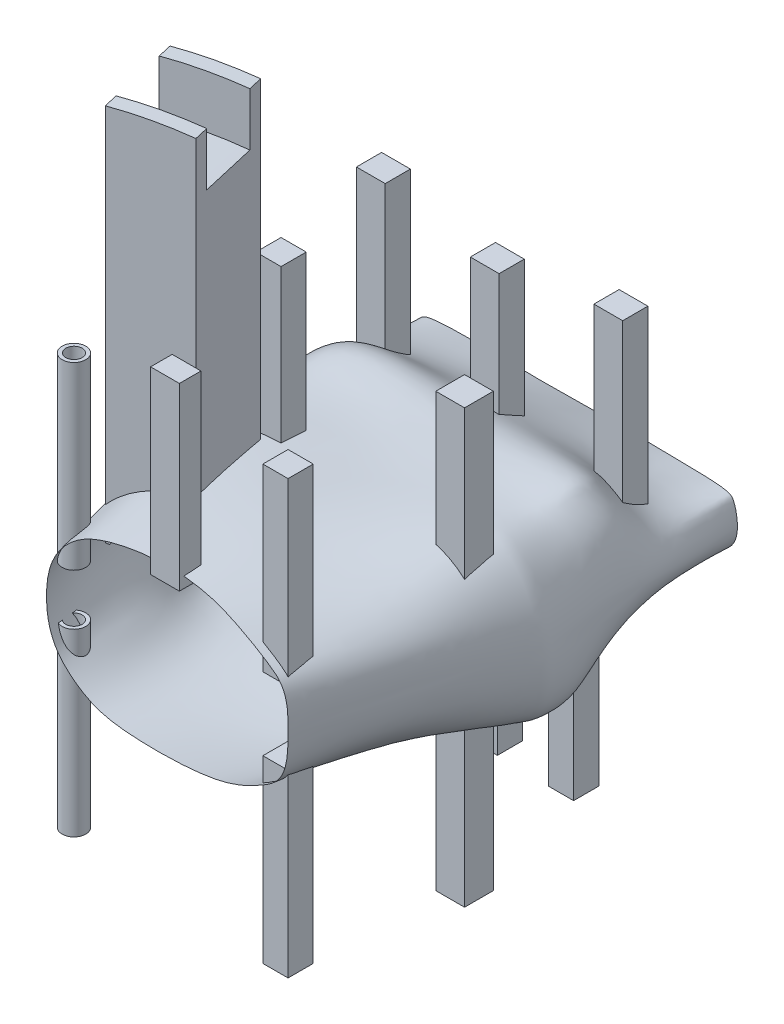
SolidWorks part; units mm, degrees
ref_plane "Front Plane" through (0, 0, 0) normal (0, 0, 1) x (1, 0, 0)
ref_plane "Top Plane" through (0, 0, 0) normal (0, 1, 0) x (1, 0, 0)
ref_plane "Right Plane" through (0, 0, 0) normal (1, 0, 0) x (0, 0, -1)
sketch "Sketch1" plane through (0, 8, 0) normal (0, 1, 0) x (1, 0, 0)
  line L1 (-4, -2.5) -> (4, -2.5)
  line L2 (-4, -2.5) -> (-4, -9.5)
  line L3 (-4, -9.5) -> (4, -9.5)
  line L4 (4, -2.5) -> (4, -9.5)
  line L5 (62, -2.5) -> (70, -2.5)
  line L6 (62, -2.5) -> (62, -9.5)
  line L7 (62, -9.5) -> (70, -9.5)
  line L8 (70, -2.5) -> (70, -9.5)
extrude "Boss-Extrude1" add sketch "Sketch1" along normal blind 50 from offset 0.1
sketch "Sketch2" plane through (0, 4, 0) normal (0, 1, 0) x (1, 0, 0)
  line L10 (37.5, -11.35) -> (37.5, -4.35)
  line L11 (37.5, -4.35) -> (29.5, -4.35)
  line L12 (29.5, -4.35) -> (29.5, -11.35)
  line L13 (29.5, -11.35) -> (33.75, -11.35)
  line L14 (33.75, -11.35) -> (37.5, -11.35)
  line L15 (37.5, -11.35) -> (37.5, -4.35)
  line L16 (37.5, -4.35) -> (29.5, -4.35)
  line L17 (29.5, -4.35) -> (29.5, -11.35)
  line L18 (29.5, -11.35) -> (33.75, -11.35)
  line L19 (33.75, -11.35) -> (37.5, -11.35)
  dimension "D1" = 0.2
extrude "Boss-Extrude2" add sketch "Sketch2" along normal blind 50 from offset 0.1 separate body
sketch "Sketch3" plane through (0, 9, 0) normal (0, 1, 0) x (1, 0, 0)
  line L1 (-9.75, -44.95) -> (-2.75, -44.95)
  line L2 (-9.75, -44.95) -> (-9.75, -51.95)
  line L3 (-9.75, -51.95) -> (-2.75, -51.95)
  line L4 (-2.75, -44.95) -> (-2.75, -51.95)
extrude "Boss-Extrude3" add sketch "Sketch3" along normal blind 50 from offset 0.1 separate body
sketch "Sketch4" plane through (0, 16, 0) normal (0, 1, 0) x (1, 0, 0)
  line L4 (17.5, -51.95) -> (17.5, -44.95)
  line L5 (17.5, -44.95) -> (10.5, -44.95)
  line L6 (10.5, -44.95) -> (10.5, -51.95)
  line L7 (10.5, -51.95) -> (17.5, -51.95)
  line L8 (17.5, -51.95) -> (17.5, -44.95)
  line L9 (17.5, -44.95) -> (10.5, -44.95)
  line L10 (10.5, -44.95) -> (10.5, -51.95)
  line L11 (10.5, -51.95) -> (17.5, -51.95)
  dimension "D1" = 0
extrude "Boss-Extrude4" add sketch "Sketch4" along normal blind 50 from offset 0.1 separate body
sketch "Sketch5" plane through (0, 8, 0) normal (0, 1, 0) x (1, 0, 0)
  line L4 (61, -52.45) -> (69, -52.45)
  line L5 (69, -52.45) -> (69, -44.45)
  line L6 (69, -44.45) -> (61, -44.45)
  line L7 (61, -44.45) -> (61, -52.45)
  line L8 (61, -52.45) -> (69, -52.45)
  line L9 (69, -52.45) -> (69, -44.45)
  line L10 (69, -44.45) -> (61, -44.45)
  line L11 (61, -44.45) -> (61, -52.45)
  dimension "D1" = 0
extrude "Boss-Extrude5" add sketch "Sketch5" along normal blind 50 from offset 0.1 separate body
sketch "Sketch6" plane through (0, 9, 0) normal (0, 1, 0) x (1, 0, 0)
  line L4 (55.5, -95) -> (62.5, -95)
  line L5 (62.5, -95) -> (62.5, -88)
  line L6 (62.5, -88) -> (55.5, -88)
  line L7 (55.5, -88) -> (55.5, -95)
  line L8 (55.5, -95) -> (62.5, -95)
  line L9 (62.5, -95) -> (62.5, -88)
  line L10 (62.5, -88) -> (55.5, -88)
  line L11 (55.5, -88) -> (55.5, -95)
  dimension "D1" = 0
extrude "Boss-Extrude6" add sketch "Sketch6" along normal blind 50 from offset 0.1 separate body
sketch "Sketch7" plane through (0, 20, 0) normal (0, 1, 0) x (1, 0, 0)
  line L8 (35.5, -92.2) -> (27.5, -92.2)
  line L9 (27.5, -92.2) -> (27.5, -98.2)
  line L10 (27.5, -98.2) -> (35.5, -98.2)
  line L11 (35.5, -98.2) -> (35.5, -92.2)
  line L12 (35.5, -92.2) -> (27.5, -92.2)
  line L13 (27.5, -92.2) -> (27.5, -98.2)
  line L14 (27.5, -98.2) -> (35.5, -98.2)
  line L15 (35.5, -98.2) -> (35.5, -92.2)
  dimension "D1" = 0.2
extrude "Boss-Extrude7" add sketch "Sketch7" along normal blind 50 from offset 0.1 separate body
sketch "Sketch8" plane through (0, 6, 0) normal (0, 1, 0) x (1, 0, 0)
  circle A0 centre (-0.5, -91.5) radius 2.275
  circle A1 centre (-0.5, -91.5) radius 3.275
  arc A2 (-1.6902, -94.5511) -> (-1.0727, -88.2755) centre (-0.5, -91.5) ccw construction
  circle A3 centre (-0.5, -91.5) radius 2.275 construction
extrude "Boss-Extrude8" add sketch "Sketch8" along normal blind 50 from offset 0.1 separate body
sketch "Sketch9" plane through (0, -12, 0) normal (0, -1, 0) x (1, 0, 0)
  line L1 (7.5, 11.65) -> (14.5, 11.65)
  line L2 (7.5, 11.65) -> (7.5, 4.65)
  line L3 (7.5, 4.65) -> (14.5, 4.65)
  line L4 (14.5, 11.65) -> (14.5, 4.65)
  line L5 (30, 11.35) -> (37, 11.35)
  line L6 (30, 11.35) -> (30, 4.35)
  line L7 (30, 4.35) -> (37, 4.35)
  line L8 (37, 11.35) -> (37, 4.35)
  line L9 (58.5, 11.65) -> (51.5, 11.65)
  line L10 (58.5, 11.65) -> (58.5, 4.65)
  line L11 (58.5, 4.65) -> (51.5, 4.65)
  line L12 (51.5, 11.65) -> (51.5, 4.65)
  line L13 (61, 52.45) -> (69, 52.45)
  line L14 (61, 52.45) -> (61, 44.45)
  line L15 (61, 44.45) -> (69, 44.45)
  line L16 (69, 52.45) -> (69, 44.45)
extrude "Boss-Extrude9" add sketch "Sketch9" along normal blind 50 from offset 0.1 separate body
sketch "Sketch10" plane through (0, -11, 0) normal (0, -1, 0) x (1, 0, 0)
  line L1 (55.5, 95) -> (62.5, 95)
  line L2 (55.5, 95) -> (55.5, 88)
  line L3 (55.5, 88) -> (62.5, 88)
  line L4 (62.5, 95) -> (62.5, 88)
  line L5 (17.5, 51.95) -> (10.5, 51.95)
  line L6 (17.5, 51.95) -> (17.5, 44.95)
  line L7 (17.5, 44.95) -> (10.5, 44.95)
  line L8 (10.5, 51.95) -> (10.5, 44.95)
extrude "Boss-Extrude10" add sketch "Sketch10" along normal blind 50 from offset 0.1 separate body
sketch "Sketch11" plane through (0, -8, 0) normal (0, -1, 0) x (1, 0, 0)
  circle A0 centre (-0.5, 91.5) radius 2.275 construction
  circle A1 centre (-0.5, 91.5) radius 3.275
  circle A2 centre (-0.5, 91.5) radius 3.275
  circle A3 centre (-0.5, 91.5) radius 2.275
  dimension "D1" = 0
extrude "Boss-Extrude11" add sketch "Sketch11" along normal blind 50 from offset 0.1 separate body
ref_plane "Plane1" through (12.8977, 0, 55.8661) normal (0.225, 0, 0.9744) x (0.9744, 0, -0.225)
ref_plane "Plane2" through (15.1472, 0, 65.6098) normal (0.225, 0, 0.9744) x (0.9744, 0, -0.225)
sketch "Sketch12" plane through (12.8977, 0, 55.8661) normal (0.225, 0, 0.9744) x (0.9744, 0, -0.225)
  circle A0 centre (-9.3704, 0) radius 10.7
  dimension "D1" = 21.4
extrude "Extrude-Thin1" add sketch "Sketch12" along normal mid plane 4 separate body thin thin type one direction wall 100
sketch "Sketch13" plane through (13.3476, 0, 57.8148) normal (0.225, 0, 0.9744) x (0.9744, 0, -0.225)
  line L0 (0.0896, 5) -> (1.1296, 5)
  line L1 (1.1296, 5) -> (1.1296, 110.2009)
  line L2 (-19.8704, 110.2009) -> (-19.8704, 5)
  line L3 (-20.0704, 6) -> (-20.0704, 0) construction
  line L4 (1.3296, 6) -> (1.3296, 0) construction
  line L5 (-19.8704, 5) -> (-18.8303, 5)
  line L6 (-15.9888, 6) -> (-22.9251, 6) construction
  circle A0 centre (-9.3704, 0) radius 10.7 construction
  circle A1 centre (-9.3704, 0) radius 110.7 construction
  arc A2 (-19.8704, 110.2009) -> (1.1296, 110.2009) centre (-9.3704, 0) ccw
  arc A3 (0.0896, 5) -> (-18.8303, 5) centre (-9.3704, 0) ccw
  dimension "D1" = 0.2
  dimension "D2" = 0.2
  dimension "D3" = 1
extrude "Cut-Extrude1" cut sketch "Sketch13" against normal through all both and the other way through all
mirror "Mirror1" about plane through (15.1472, 0, 65.6098) normal (0.225, 0, 0.9744) of bodies 118
sketch "Sketch14" plane through (17.8466, 0, 77.3022) normal (0.225, 0, 0.9744) x (0.9744, 0, -0.225)
  circle A0 centre (-9.3704, 0) radius 16
  dimension "D1" = 32
extrude "Extrude-Thin2" add sketch "Sketch14" against normal up to surface (24 mm away) thin up to face at (3.3176, 41.1002, 56.0252) thin type one direction wall 80
extrude "Cut-Extrude2" cut sketch "Sketch13<3>" against normal through all both and the other way through all
sketch "Sketch13<3>" plane through (13.3476, 0, 57.8148) normal (0.225, 0, 0.9744) x (0.9744, 0, -0.225) same geometry as "Sketch13"
fillet "Fillet1" radius 0.5 2 edges at (16.2479, 12.0727, 65.3557) (-4.2139, 12.0727, 70.0796)
ref_plane "Plane3" through (0, 0, 0) normal (0, 1, 0) x (1, 0, 0)
sketch "Sketch15" plane through (0, 0, 0) normal (0, 1, 0) x (1, 0, 0)
  line L0 (-12.1525, 15) -> (-15.2953, -40.3087)
  line L1 (-15.0551, -43.1255) -> (-2.294, -98.4)
  line L2 (64.1595, -98.4) -> (79.2818, -41.9628)
  line L3 (79.614, -38.9613) -> (77.3822, 15)
  line L4 (76.3839, -33.4595) -> (75, 0) construction
  line L5 (76.7992, -43.5006) -> (63.0268, -94.9) construction
  line L6 (-12.3568, -41.4768) -> (-8.5998, -57.7502) construction
  line L7 (-10, 0) -> (-12.2621, -39.8092) construction
  line L9 (64.1595, -98.4) -> (65.0973, -94.9)
  line L10 (-2.294, -98.4) -> (-3.102, -94.9)
  line L12 (75, 0) -> (47, 0) construction
  arc A0 (79.2818, -41.9628) -> (79.614, -38.9613) centre (69.6226, -39.3746) ccw
  arc A1 (-15.2953, -40.3087) -> (-15.0551, -43.1255) centre (-5.3114, -40.876) ccw
  point P14 (0, 0)
  point P24 (0, 0)
  point P25 (63.9468, -99.1937)
  point P26 (0, 0)
  point P28 (0, 0)
  point P30 (0, 0)
  point P32 (0, 0)
  point P33 (-11.5291, 25.9717)
  point P34 (0, 0)
  point P35 (77.212, 19.1146)
  point P36 (77.0804, 22.2963)
  dimension "D5" = 10
  dimension "D1" = 3
  dimension "D2" = 2
  dimension "D3" = 3
  dimension "D4" = 3
  dimension "D6" = 15
ref_plane "Plane4" through (0, 0, -15) normal (0, 0, -1) x (-1, 0, 0)
ref_plane "Plane5" through (0, 0, 41.97) normal (0, 0, 1) x (1, 0, 0)
ref_plane "Plane6" through (0, 0, 29.03) normal (0, 0, -1) x (-1, 0, 0)
ref_plane "Plane7" through (0, 0, 67.45) normal (0, 0, 1) x (1, 0, 0)
ref_plane "Plane8" through (0, 0, 97) normal (0, 0, 1) x (1, 0, 0)
sketch "Sketch16" plane through (0, 0, -15) normal (0, 0, -1) x (-1, 0, 0)
  line L0 (-64.1595, 0) -> (-79.2818, 0) construction
  line L1 (-79.614, 0) -> (-77.3822, 0) construction
  line L2 (15.0551, 0) -> (2.294, 0) construction
  spline S0 degree 3 poles (-71.1852, -9.0827) (-78.6693, -4.8815) (-76.8048, 5.1779) (-74.9375, 7.6273) (-44.2299, 7.9457) (-51.3054, 8.2091) (-16.6288, 7.6603) (-20.5035, 8.0278) (8.9045, 8.0076) (11.3889, 5.5481) (12.2889, 1.7755) (11.9298, -3.3745) (11.1196, -8.9657) (-11.6903, -7.8226) (-16.6557, -9.5364) (-48.9186, -8.3026) (-56.5707, -7.9846) (-71.1852, -9.0827) (-78.6693, -4.8815) (-76.8048, 5.1779) knots -0.231953 -0.094003 -0.053059 0 0.019528 0.023803 0.04275 0.118919 0.206181 0.302051 0.336436 0.343183 0.366589 0.374014 0.414502 0.467056 0.636571 0.768047 0.905997 0.946941 1 1.019528 1.023803 1.04275 only from (-77.3822, 0) to (-77.3822, 0)
  point P2 (-75.5767, 6.9122)
  point P4 (-75.1062, -8.6557)
  point P6 (-69.5004, 9.0908)
  point P8 (-75.1149, 6.9745)
  point P10 (-74.5535, -8.0983)
  point P12 (-66.4034, 8.5614)
  point P14 (-46.5361, 8.2128)
  point P16 (-64.2424, 8.0386)
  point P18 (-46.2922, 7.8991)
  point P20 (-24.0813, 7.8368)
  point P22 (-5.1953, 8.0021)
  point P24 (10.798, 5.7457)
  point P26 (10.5557, 6.1817)
  point P27 (0, 0)
  point P34 (-65.2276, -9.6842)
  point P35 (-73.9069, -8.1232)
  point P37 (10.6701, -7.0069)
  point P38 (-63.0421, -8.4978)
  point P39 (-45.3088, -8.4354)
  point P40 (-24.1411, -9.1222)
  point P41 (1.441, -8.5356)
  point P42 (-23.1641, -8.4925)
  point P43 (-22.8662, -8.9897)
  point P44 (-0.6234, -8.4463)
  point P45 (9.8283, -7.237)
  point P46 (10.3898, 6.497)
  point P47 (0, 0)
  point P49 (-70.4738, -8.281)
  point P50 (-75.8251, 6.4125)
  point P51 (-44.7505, 8.0667)
  point P52 (-63.2214, 7.7557)
ref_plane "Plane9" through (0, 0, 6) normal (0, 0, -1) x (-1, 0, 0)
ref_plane "Plane10" through (0, 0, 14.03) normal (0, 0, -1) x (-1, 0, 0)
sketch "Sketch17" plane through (0, 0, 6) normal (0, 0, -1) x (-1, 0, 0)
  spline S0 degree 3 poles (-67.8201, -15.6001) (-81.0048, -1.3111) (-73.2807, 12.2207) (-57.6326, 16.4911) (-36.4637, 17.5746) (-14.0249, 16.8961) (9.2014, 14.5539) (14.6409, 0.0272) (10.0445, -10.7561) (-5.7019, -14.242) (-24.5254, -13.8435) (-47.1853, -13.9578) (-67.8201, -15.6001) (-81.0048, -1.3111) (-73.2807, 12.2207) knots -0.282804 -0.175267 -0.065396 0 0.049153 0.124956 0.221485 0.350059 0.461159 0.505948 0.550346 0.60994 0.717196 0.824733 0.934604 1 1.049153 1.124956 1.221485 only from (-78.2507, 0) to (-78.2507, 0)
  point P2 (0, 0)
  point P4 (10.3011, 8.9171)
  point P6 (9.6866, -8.5937)
  point P8 (0, 0)
  point P10 (9.9938, -8.3743)
  point P12 (-4.6643, -12.9824)
  point P14 (-24.5041, -14.2451)
  point P16 (-47.191, -14.2471)
  point P18 (-70.0862, -11.073)
  point P20 (-73.7806, 9.3245)
  point P22 (-59.1069, 15.5686)
  point P23 (-11.8304, 16.4321)
  point P26 (-24.57, -13.9405)
  point P27 (-2.0228, -13.0733)
sketch "Sketch18" plane through (0, 0, 14.03) normal (0, 0, -1) x (-1, 0, 0)
  spline S0 degree 3 poles (-78.1744, -5.7209) (-78.8867, 3.3384) (-75.8875, 10.8583) (-72.3342, 15.9421) (-69.0351, 18.3111) (-64.1979, 22.009) (-39.0825, 20.8471) (-20.663, 22.2437) (4.4452, 22.3694) (16.2899, 4.0467) (11.6003, -19.0656) (-3.4549, -17.7642) (-24.9715, -18.5851) (-44.1357, -17.5762) (-72.3303, -16.6356) (-78.1744, -5.7209) (-78.8867, 3.3384) (-75.8875, 10.8583) knots -0.173726 -0.091095 -0.009109 0 0.068298 0.084008 0.148983 0.166724 0.253293 0.360225 0.438075 0.532552 0.595553 0.656082 0.718049 0.826274 0.908905 0.990891 1 1.068298 1.084008 1.148983 only from (-78.5829, 0) to (-78.5829, 0)
  point P2 (0, 0)
  point P4 (-66.8285, 20.2511)
  point P6 (-42.5875, 21.6094)
  point P8 (0, 0)
  point P10 (-74.0903, 13.4072)
  point P12 (-17.3256, 22.1027)
  point P14 (1.5583, 19.6078)
  point P16 (-66.966, 19.8659)
  point P18 (-43.4793, 21.3715)
  point P20 (0, 0)
  point P22 (7.6781, -13.0552)
  point P23 (-19.9094, -16.5923)
  point P26 (-4.3134, -15.5113)
  point P27 (-20.1024, -15.3183)
  point P28 (-4.5837, -15.2025)
  point P29 (7.924, -12.1914)
  point P30 (-46.7061, -15.7012)
  point P31 (-68.097, -14.8419)
  point P32 (-3.7064, -14.8738)
  point P33 (-69.5062, -14.1704)
  point P34 (9.3546, -14.6553)
  point P35 (-3.7101, -16.9519)
  point P36 (-20.0241, -16.973)
  point P37 (9.6305, -15.6958)
  point P38 (-3.7001, -18.0905)
  point P39 (-20.2636, -18.2502)
  point P40 (-47.7655, -17.5074)
sketch "Sketch19" plane through (0, 0, 29.03) normal (0, 0, -1) x (-1, 0, 0)
  spline S0 degree 3 poles (-79.171, -20.3631) (-80.7638, -0.0393) (-75.5328, 14.2924) (-67.5362, 20.7237) (-56.7767, 23.0714) (-38.5157, 22.4921) (-17.4291, 23.1266) (5.9183, 21.7112) (17.2856, 2.3447) (13.4244, -11.838) (9.5174, -21.2535) (0.1006, -21.5099) (-11.9829, -21.6909) (-28.8316, -21.4847) (-47.7412, -21.657) (-62.671, -22.9052) (-79.171, -20.3631) (-80.7638, -0.0393) (-75.5328, 14.2924) knots -0.191554 -0.118168 -0.086598 0 0.071895 0.105684 0.119135 0.2064 0.329313 0.384742 0.484271 0.550555 0.566403 0.603602 0.648592 0.724046 0.808446 0.881832 0.913402 1 1.071895 1.105684 1.119135 only from (-79.2033, 0) to (-79.2033, 0)
  point P2 (0, 0)
  point P4 (1.138, -20.0455)
  point P6 (-10.409, -21.1383)
  point P8 (0, 0)
  point P10 (9.516, -20.1184)
  point P12 (11.738, -15.8201)
  point P14 (0, 0)
  point P16 (9.9167, -19.2077)
  point P18 (1.138, -20.7376)
  point P20 (0, 0)
  point P22 (-28.0538, -21.5558)
  point P24 (-48.5336, -21.9294)
  point P26 (-66.3422, -22.1617)
  point P28 (-72.6139, -20.6131)
  point P29 (-9.7418, -21.6197)
  point P32 (1.1756, -21.4648)
  point P33 (-73.7753, -20.3034)
  point P34 (0, 0)
  point P35 (-72.5439, 16.1274)
  point P36 (-64.9898, 21.2221)
  point P37 (-11.6791, 22.6539)
  point P38 (1.5657, 20.3012)
sketch "Sketch20" plane through (0, 0, 41.97) normal (0, 0, 1) x (1, 0, 0)
  spline S0 degree 3 poles (-13.7918, -14.018) (-17.4972, -1.0196) (-11.9374, 10.2837) (-5.1797, 19.1082) (3.1572, 22.1096) (21.6152, 23.5732) (39.0515, 22.136) (57.9967, 23.4248) (70.1604, 19.6682) (76.8965, 11.3257) (80.3663, -2.3328) (79.808, -20.8805) (61.4518, -21.9017) (46.2737, -22.2041) (26.9211, -21.9961) (11.4125, -21.526) (-0.0103, -21.683) (-7.9367, -21.8247) (-13.7918, -14.018) (-17.4972, -1.0196) (-11.9374, 10.2837) knots -0.121971 -0.087846 -0.075649 0 0.058041 0.072558 0.137106 0.15903 0.283733 0.368469 0.38409 0.439936 0.484587 0.568827 0.605034 0.689826 0.764361 0.842217 0.878029 0.912154 0.924351 1 1.058041 1.072558 1.137106 only from (-15.2514, 0) to (-15.2514, 0)
  spline S1 degree 3 poles (79.171, -20.3631) (80.7638, -0.0393) (75.5328, 14.2924) (67.5362, 20.7237) (56.7767, 23.0714) (38.5157, 22.4921) (17.4291, 23.1266) (-5.9183, 21.7112) (-17.2856, 2.3447) (-13.4244, -11.838) (-9.5174, -21.2535) (-0.1006, -21.5099) (11.9829, -21.6909) (28.8316, -21.4847) (47.7412, -21.657) (62.671, -22.9052) (79.171, -20.3631) (80.7638, -0.0393) (75.5328, 14.2924) knots -0.191554 -0.118168 -0.086598 0 0.071895 0.105684 0.119135 0.2064 0.329313 0.384742 0.484271 0.550555 0.566403 0.603602 0.648592 0.724046 0.808446 0.881832 0.913402 1 1.071895 1.105684 1.119135 only from (79.2033, 0) to (79.2033, 0) construction
  point P2 (0, 0)
  point P4 (0, 0)
  point P6 (45.2983, -22.1106)
  point P8 (0, 0)
  point P10 (74.5754, -19.9509)
  point P12 (0, 0)
  point P14 (27.1625, -21.9399)
  point P16 (8.3977, -22.0537)
  point P18 (-5.7984, -20.8555)
  point P20 (-9.7922, -19.8753)
  point P22 (-0.4931, -21.6969)
  point P24 (-9.4832, -19.6228)
  point P27 (8.2207, -21.6108)
  point P30 (76.3285, 10.4565)
  point P31 (65.5625, 21.0431)
  point P32 (42.7181, 22.7741)
  point P33 (9.0033, 22.5386)
  point P34 (-8.825, 14.3161)
sketch "Sketch21" plane through (0, 0, 67.45) normal (0, 0, 1) x (1, 0, 0)
  spline S0 degree 3 poles (72.0226, -9.858) (72.6835, -0.2396) (71.9233, 9.6159) (61.9224, 19.1374) (43.786, 23.8713) (29.8096, 24.6807) (11.4977, 23.7767) (1.1455, 20.6848) (-9.0886, 10.6402) (-10.4839, -2.3394) (-4.23, -12.4476) (6.095, -20.6415) (24.7956, -24.2725) (42.7476, -24.5128) (58.4196, -21.637) (65.3855, -16.9346) (72.0226, -9.858) (72.6835, -0.2396) (71.9233, 9.6159) knots -0.130522 -0.090139 -0.044745 0 0.041447 0.0902 0.182445 0.293673 0.315758 0.403301 0.458698 0.503428 0.577284 0.614864 0.687699 0.838111 0.869478 0.909861 0.955255 1 1.041447 1.0902 1.182445 only from (72.4526, 0) to (72.4526, 0)
  point P2 (0, 0)
  point P4 (69.7591, 18.7365)
  point P6 (64.0184, 16.3042)
  point P8 (71.0278, 8.6854)
  point P10 (0, 0)
  point P12 (20.125, 21.3824)
  point P14 (0, 0)
  point P16 (-0.4315, 18.2175)
  point P18 (0, 0)
  point P20 (46.2746, 21.8493)
  point P22 (71.008, -9.3912)
  point P24 (64.9237, -16.8682)
  point P26 (57.6316, -21.3808)
  point P28 (49.4493, -22.5497)
  point P29 (19.0107, -22.6843)
  point P30 (18.4436, -23.3402)
  point P31 (-8.2447, 9.4233)
  point P33 (4.6489, -20.4176)
  point P34 (0, 0)
  point P35 (-11.7223, 9.9754)
  point P36 (4.32, -18.6831)
  point P38 (-1.9948, -13.8039)
  point P39 (19.2052, -22.8842)
  point P40 (51.1457, -22.8966)
  point P41 (20.2924, 22.3816)
  point P42 (0, 0)
  point P43 (19.5313, 23.4501)
  point P44 (45.5667, 22.8802)
  point P45 (19.3536, 24.1502)
sketch "Sketch23" plane through (0, 0, 97) normal (0, 0, 1) x (1, 0, 0)
  spline S0 degree 3 poles (-1.7622, -11.0322) (-3.0627, -1.2714) (-1.7373, 8.928) (5.1339, 17.869) (16.785, 21.9242) (28.6762, 23.6082) (38.7998, 23.1123) (46.7462, 20.695) (53.1142, 17.4728) (58.1841, 14.5114) (64.4308, 9.872) (64.6852, -0.596) (64.1983, -12.1853) (56.235, -16.9491) (47.9884, -21.1109) (35.7099, -22.7051) (22.7771, -22.749) (12.3318, -21.6135) (4.9204, -17.5797) (-1.7622, -11.0322) (-3.0627, -1.2714) (-1.7373, 8.928) knots -0.146785 -0.109783 -0.0633 0 0.04164 0.103384 0.171354 0.237511 0.299646 0.334713 0.372416 0.415626 0.431444 0.496386 0.569876 0.603538 0.640162 0.721933 0.800387 0.853215 0.890217 0.9367 1 1.04164 1.103384 1.171354 only from (-2.6172, 0) to (-2.6172, 0)
  point P2 (5.454, 16.6191)
  point P4 (40.3554, 22.439)
  point P6 (52.768, 17.576)
  point P8 (0, 0)
  point P10 (0, 0)
  point P12 (56.4177, -16.758)
  point P14 (-0.7988, 10.0871)
  point P16 (0, 0)
  point P18 (0, 0)
  point P20 (61.8045, 11.6161)
  point P22 (-0.2696, -11.3916)
  point P24 (-1.358, 7.5467)
surface "Surface-Loft1"
